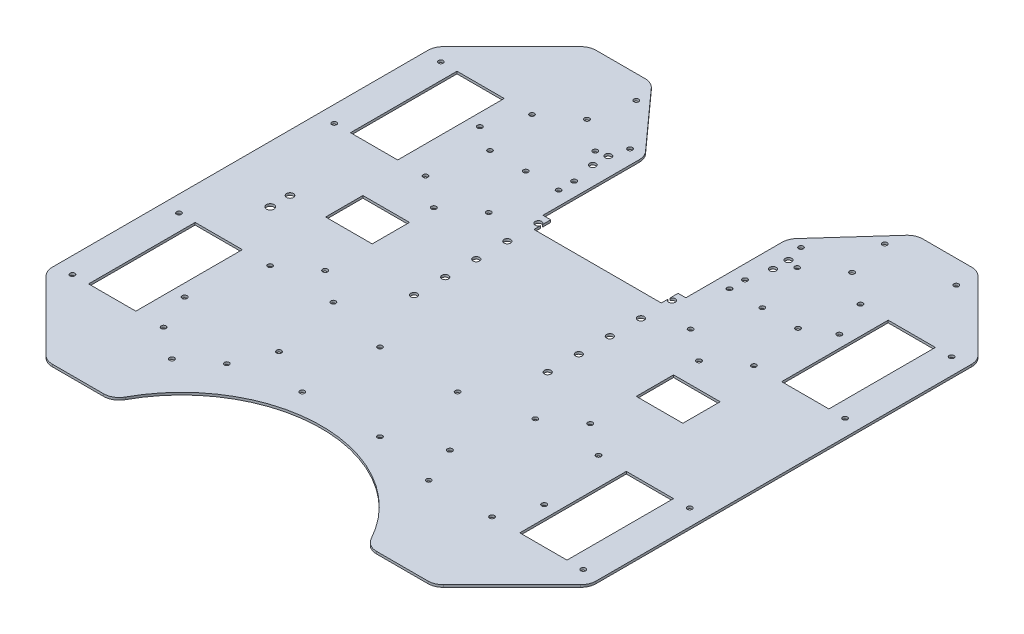
SolidWorks part; units mm, degrees
material "PMMA"
ref_plane "前视基准面" through (0, 0, 0) normal (0, 0, 1) x (1, 0, 0)
ref_plane "上视基准面" through (0, 0, 0) normal (0, 1, 0) x (1, 0, 0)
ref_plane "右视基准面" through (0, 0, 0) normal (1, 0, 0) x (0, 0, -1)
other "Configuration Table"
sketch "草图1" plane through (0, 0, 0) normal (0, 1, 0) x (1, 0, 0)
  line L0 (-125, 175) -> (-175, 125)
  line L1 (125, -175) -> (81.7103, -175)
  line L2 (175, -125) -> (175, 125)
  line L3 (125, 175) -> (85, 175)
  line L4 (-175, -125) -> (-175, 125)
  line L5 (-85, 175) -> (-40, 125)
  line L7 (125, 175) -> (175, 125)
  line L8 (175, -125) -> (125, -175)
  line L9 (-125, -175) -> (-175, -125)
  line L10 (40, 125) -> (85, 175)
  line L11 (-85, 175) -> (-125, 175)
  line L12 (40, 125) -> (40, 85)
  line L13 (40, 85) -> (-40, 85)
  line L14 (-40, 85) -> (-40, 125)
  line L15 (-153.994, 50) -> (-123.594, 50)
  line L16 (-123.594, 50) -> (-123.594, 118.58)
  line L17 (-123.594, 118.58) -> (-153.994, 118.58)
  line L18 (-153.994, 118.58) -> (-153.994, 50)
  line L19 (123.594, 50) -> (153.994, 50)
  line L20 (153.994, 50) -> (153.994, 118.58)
  line L21 (153.994, 118.58) -> (123.594, 118.58)
  line L22 (123.594, 118.58) -> (123.594, 50)
  line L23 (-175, 0) -> (175, 0) construction
  line L24 (-123.594, -118.58) -> (-153.994, -118.58)
  line L25 (-123.594, -50) -> (-123.594, -118.58)
  line L26 (-153.994, -50) -> (-123.594, -50)
  line L27 (-153.994, -118.58) -> (-153.994, -50)
  line L28 (153.994, -118.58) -> (123.594, -118.58)
  line L29 (153.994, -50) -> (153.994, -118.58)
  line L30 (123.594, -50) -> (153.994, -50)
  line L31 (123.594, -118.58) -> (123.594, -50)
  line L32 (-81.7103, -175) -> (-125, -175)
  line L33 (-80, 160) -> (-55, 131) construction
  line L34 (0, 85) -> (0, -124.4881) construction
  line L35 (-40, 85) -> (-40, -25)
  line L36 (-40, -25) -> (40, -25)
  line L37 (40, -25) -> (40, 85)
  line L38 (-40, -25) -> (-40, 66.9577)
  line L39 (-40, 66.9577) -> (40, 66.9577)
  line L40 (40, 66.9577) -> (40, -25)
  line L41 (-85.36, -35) -> (-85.36, -133.58)
  circle A0 centre (-55, 131) radius 1.55
  circle A1 centre (-80, 160) radius 1.55
  circle A2 centre (55, 131) radius 1.55
  circle A3 centre (80, 160) radius 1.55
  circle A4 centre (-65, 118.58) radius 1.55
  circle A5 centre (-65, 50) radius 1.55
  circle A6 centre (-105.72, 50) radius 1.55
  circle A7 centre (-105.72, 118.58) radius 1.55
  circle A12 centre (-164.434, 118.58) radius 1.55
  circle A13 centre (-164.434, 50) radius 1.55
  circle A14 centre (-65, -118.58) radius 1.55
  circle A15 centre (-65, -50) radius 1.55
  circle A16 centre (-105.72, -50) radius 1.55
  circle A17 centre (-105.72, -118.58) radius 1.55
  circle A18 centre (-164.434, -50) radius 1.55
  circle A19 centre (-164.434, -118.58) radius 1.55
  circle A20 centre (65, 50) radius 1.55
  circle A21 centre (105.72, 50) radius 1.55
  circle A22 centre (105.72, 118.58) radius 1.55
  circle A23 centre (65, 118.58) radius 1.55
  circle A24 centre (164.434, 118.58) radius 1.55
  circle A25 centre (164.434, 50) radius 1.55
  circle A26 centre (164.434, -118.58) radius 1.55
  circle A27 centre (164.434, -50) radius 1.55
  circle A28 centre (105.72, -50) radius 1.55
  circle A29 centre (105.72, -118.58) radius 1.55
  circle A30 centre (65, -118.58) radius 1.55
  circle A31 centre (65, -50) radius 1.55
  arc A32 (-81.7103, -175) -> (81.7103, -175) centre (0, -212.7283) cw
  circle A33 centre (25, -60) radius 1.55
  circle A34 centre (25, -110) radius 1.55
  circle A35 centre (-25, -60) radius 1.55
  circle A36 centre (-25, -110) radius 1.55
  circle A37 centre (-43, 120) radius 2.05
  circle A38 centre (-43, 110) radius 2.05
  circle A39 centre (-58, 110) radius 2.05
  circle A40 centre (-58, 120) radius 2.05
  circle A41 centre (43, 120) radius 2.05
  circle A42 centre (58, 120) radius 2.05
  circle A43 centre (58, 110) radius 2.05
  circle A44 centre (43, 110) radius 2.05
  circle A45 centre (43, -20) radius 2.1
  circle A46 centre (43, 0) radius 2.1
  circle A47 centre (43, 20) radius 2.1
  circle A48 centre (43, 40) radius 2.1
  circle A49 centre (43, 60) radius 2.1
  circle A50 centre (-43, -20) radius 2.1
  circle A51 centre (-43, 0) radius 2.1
  circle A52 centre (-43, 20) radius 2.1
  circle A53 centre (-43, 40) radius 2.1
  circle A54 centre (-43, 60) radius 2.1
  circle A55 centre (-138.4729, -4.4575) radius 2.205
  circle A56 centre (-138.4729, -17.1575) radius 2.5
  circle A57 centre (126, 160) radius 1.55
  circle A58 centre (-55, 85) radius 1.55
  circle A59 centre (-76.1355, 85) radius 1.55
  circle A60 centre (-99.1475, 85) radius 1.55
  circle A61 centre (55, 85) radius 1.55
  circle A62 centre (76.1355, 85) radius 1.55
  circle A63 centre (99.1475, 85) radius 1.55
  circle A64 centre (-85.36, -35) radius 1.6
  circle A65 centre (-85.36, -133.58) radius 1.6
  circle A66 centre (-55, -95) radius 1.6
  circle A67 centre (-115.72, -95) radius 1.6
  circle A68 centre (85.36, -133.58) radius 1.6
  circle A69 centre (55, -95) radius 1.6
  circle A70 centre (115.72, -95) radius 1.6
  circle A71 centre (85.36, -35) radius 1.6
  circle A72 centre (85.36, 133.58) radius 1.6
  circle A73 centre (115.72, 95) radius 1.6
  circle A74 centre (55, 95) radius 1.6
  circle A75 centre (85.36, 35) radius 1.6
  circle A76 centre (-85.36, 35) radius 1.6
  circle A77 centre (-55, 95) radius 1.6
  circle A78 centre (-115.72, 95) radius 1.6
  circle A79 centre (-85.36, 133.58) radius 1.6
  point P0 (0, 0)
  point P1 (-85, 175)
  point P2 (85, 175)
  point P3 (40, 125)
  point P4 (-40, 125)
  point P6 (125, 175)
  point P8 (175, 125)
  point P10 (175, -125)
  point P11 (125, -175)
  point P12 (-125, -175)
  point P13 (-175, -125)
  point P24 (-80, 160)
  point P25 (-55, 131)
  point P26 (55, 131)
  point P27 (80, 160)
  point P36 (-164.434, 118.58)
  point P37 (-164.434, 50)
  point P38 (-153.994, 118.58)
  point P39 (-123.594, 50)
  point P40 (-105.72, 118.58)
  point P41 (-105.72, 50)
  point P42 (-65, 118.58)
  point P43 (-65, 50)
  point P47 (-123.594, 118.58)
  point P53 (-153.994, 50)
  point P66 (-40, 85)
  point P67 (40, 85)
  point P70 (105.72, 50)
  point P71 (65, 50)
  point P72 (123.594, 50)
  point P73 (153.994, 50)
  point P74 (164.434, 50)
  point P75 (65, 118.58)
  point P76 (105.72, 118.58)
  point P77 (123.594, 118.58)
  point P78 (153.994, 118.58)
  point P81 (164.434, 118.58)
  point P85 (-65, -118.58)
  point P88 (-65, -50)
  point P91 (-105.72, -50)
  point P94 (-105.72, -118.58)
  point P101 (-164.434, -50)
  point P104 (-164.434, -118.58)
  point P118 (164.434, -118.58)
  point P121 (164.434, -50)
  point P128 (105.72, -50)
  point P131 (105.72, -118.58)
  point P134 (65, -118.58)
  point P137 (65, -50)
  point P157 (58, 110)
  point P158 (43, 110)
  point P159 (43, 120)
  point P160 (58, 120)
  point P189 (-43, 60)
  dimension "D29" = 3.1
  dimension "D30" = 3.1
  dimension "D31" = 3.1
  dimension "D32" = 3.1
  dimension "D40" = 3.1
  dimension "D41" = 3.1
  dimension "D42" = 3.1
  dimension "D43" = 3.1
  dimension "D44" = 3.1
  dimension "D45" = 3.1
  dimension "D46" = 3.1
  dimension "D47" = 3.1
  dimension "D48" = 3.1
  dimension "D49" = 3.1
  dimension "D60" = 3.1
  dimension "D61" = 3.1
  dimension "D62" = 43.2897
  dimension "D63" = 90
  dimension "D67" = 3.1
  dimension "D68" = 3.1
  dimension "D69" = 3.1
  dimension "D70" = 3.1
  dimension "D75" = 4.1
  dimension "D76" = 4.1
  dimension "D77" = 4.1
  dimension "D78" = 4.1
  dimension "D80" = 110
  dimension "D83" = 5
  dimension "D85" = 20
  dimension "D89" = 4.41
  dimension "D90" = 5
  dimension "D37" = 3.1
  dimension "D56" = 3.1
  dimension "D57" = 3.1
  dimension "D92" = 3.1
  dimension "D93" = 20.36
  dimension "D97" = 45
  dimension "D1" = 175
  dimension "D2" = 175
  dimension "D3" = 125
  dimension "D4" = 125
  dimension "D5" = 125
  dimension "D6" = 125
  dimension "D7" = 125
  dimension "D8" = 125
  dimension "D9" = 125
  dimension "D10" = 125
  dimension "D11" = 175
  dimension "D12" = 175
  dimension "D13" = 40
  dimension "D14" = 40
  dimension "D15" = 85
  dimension "D16" = 85
  dimension "D17" = 125
  dimension "D18" = 125
  dimension "D19" = 40
  dimension "D20" = 45
  dimension "D21" = 160
  dimension "D22" = 160
  dimension "D23" = 80
  dimension "D24" = 80
  dimension "D25" = 55
  dimension "D26" = 131
  dimension "D27" = 55
  dimension "D28" = 131
  dimension "D33" = 50
  dimension "D34" = 118.58
  dimension "D35" = 65
  dimension "D36" = 46
  dimension "D38" = 30.4
  dimension "D39" = 10.44
  dimension "D50" = 40
  dimension "D51" = 40
  dimension "D52" = 85
  dimension "D53" = 85
  dimension "D54" = 138.013
  dimension "D55" = 65
  dimension "D58" = 30.4
  dimension "D59" = 10.44
  dimension "D64" = 0
  dimension "D65" = 25
  dimension "D66" = 25
  dimension "D71" = 60
  dimension "D72" = 50
  dimension "D73" = 15
  dimension "D74" = 10
  dimension "D79" = 43
  dimension "D81" = 120
  dimension "D82" = 110
  dimension "D84" = 3
  dimension "D86" = 20
  dimension "D87" = 20
  dimension "D88" = 20
  dimension "D91" = 12.7
  dimension "D94" = 20.36
  dimension "D95" = 15
  dimension "D96" = 15
extrude "凸台-拉伸1" add sketch "草图1" along normal blind 1.5 contours A55 | A56 | A1 | A0 | L8 L1 A32 L32 L9 L4 L0 L11 L5 L14 L13 L12 L10 L3 L7 L2 | A5 | A3 | A2 | A4 | A7 | A12 | L16 L17 L18 L15 | A6 | L21 L22 L19 L20 | A13 | A16 | A17 | A14 | A15 | A18 | A19 | L25 L24 L27 L26 | A20 | A21 | A22 | A23 | A24 | A25 | A28 | A26 | A27 | L28 L31 L30 L29 | A30 | A31 | A29 | A35 | A36 | A33 | A34 | A39 | A40 | A37 | A38 | A43 | A42 | A41 | A44 | A57 | A60 | A58 | A59 | A61 | A62 | A63 region at (-138.4729, 0, 4.4575) region at (-138.4729, 0, 17.1575)
fillet "圆角1" radius 10 1 edges at (-40, 0.75, -125)
fillet "圆角2" radius 10 1 edges at (40, 0.75, -125)
fillet "圆角3" radius 10 12 edges at (-85, 0.75, -175) (85, 0.75, -175) (125, 0.75, -175) (175, 0.75, -125) (175, 0.75, 125) (125, 0.75, 175) (81.7103, 0.75, 175) (-81.7103, 0.75, 175) (-125, 0.75, 175) (-175, 0.75, 125) (-175, 0.75, -125) (-125, 0.75, -175)
sketch "草图2" plane through (0, 1.5, 0) normal (0, 1, 0) x (1, 0, 0)
  line L1 (-40, 85) -> (40, 85)
  line L2 (-40, 85) -> (-40, 55.3716)
  line L3 (-40, 55.3716) -> (40, 55.3716)
  line L4 (40, 85) -> (40, 55.3716)
extrude "切除-拉伸1" cut sketch "草图2" against normal blind 10
sketch "草图3" plane through (0, 1.5, 0) normal (0, 1, 0) x (1, 0, 0)
  line L0 (-87.875, -175) -> (-120.8579, -175) construction
  line L1 (-115, 19) -> (-85, 19)
  line L2 (-115, 19) -> (-115, -5)
  line L3 (-115, -5) -> (-85, -5)
  line L4 (-85, 19) -> (-85, -5)
  line L5 (-175, -120.8579) -> (-175, 120.8579) construction
  line L6 (120.8579, -175) -> (87.875, -175) construction
  line L7 (85, 19) -> (115, 19)
  line L8 (85, 19) -> (85, -5)
  line L9 (85, -5) -> (115, -5)
  line L10 (115, 19) -> (115, -5)
  line L11 (175, -120.8579) -> (175, 120.8579) construction
  dimension "D1" = 30
  dimension "D2" = 24
  dimension "D3" = 170
  dimension "D4" = 60
  dimension "D5" = 30
  dimension "D6" = 24
  dimension "D7" = 170
  dimension "D8" = 60
extrude "切除-拉伸2" cut sketch "草图3" against normal blind 10
extrude "切除-拉伸3" cut sketch "草图1<4>" along normal blind 10 contours A54 | A53 | A52 | A51 | A50 | A49 | A48 | A47 | A46 | A45
sketch "草图1<4>" plane through (0, 0, 0) normal (0, 1, 0) x (1, 0, 0) same geometry as "草图1"
sketch "草图5" plane through (0, 0, 0) normal (0, -1, 0) x (1, 0, 0)
  line L0 (-40, -55.3716) -> (-40, -121.1626) construction
  line L1 (-46, -65.9277) -> (46, -65.9277)
  line L2 (-46, -65.9277) -> (-46, -134.4558)
  line L3 (-46, -134.4558) -> (46, -134.4558)
  line L4 (46, -65.9277) -> (46, -134.4558)
  line L5 (40, -121.1626) -> (40, -55.3716) construction
  dimension "D1" = 6
  dimension "D2" = 6
extrude "切除-拉伸4" cut sketch "草图5" against normal blind 4
sketch "草图6" plane through (0, 1.5, 0) normal (0, 1, 0) x (1, 0, 0)
  line L0 (-40, 65.9277) -> (-46, 65.9277) construction
  line L1 (-41, 65.9277) -> (41, 65.9277)
  line L2 (-41, 65.9277) -> (-41, 55.1146)
  line L3 (-41, 55.1146) -> (41, 55.1146)
  line L4 (41, 65.9277) -> (41, 55.1146)
  line L5 (-40, 55.3716) -> (-40, 65.9277) construction
  line L6 (40, 65.9277) -> (40, 55.3716) construction
  dimension "D1" = 1
  dimension "D2" = 1
extrude "切除-拉伸5" cut sketch "草图6" against normal blind 10
fillet "圆角4" radius 10 2 edges at (46, 0.75, -131.6667) (-46, 0.75, -131.6667)
extrude "切除-拉伸7" cut sketch "草图1<5>" along normal blind 10 contours A79 | A78 | A77 | A76 | A64 | A67 | A65 | A72 | A74 | A73 | A75 | A71 | A69 | A70
sketch "草图1<5>" plane through (0, 0, 0) normal (0, 1, 0) x (1, 0, 0) same geometry as "草图1"
extrude "切除-拉伸8" cut sketch "草图1<6>" along normal blind 10 contours A66
sketch "草图1<6>" plane through (0, 0, 0) normal (0, 1, 0) x (1, 0, 0) same geometry as "草图1"
